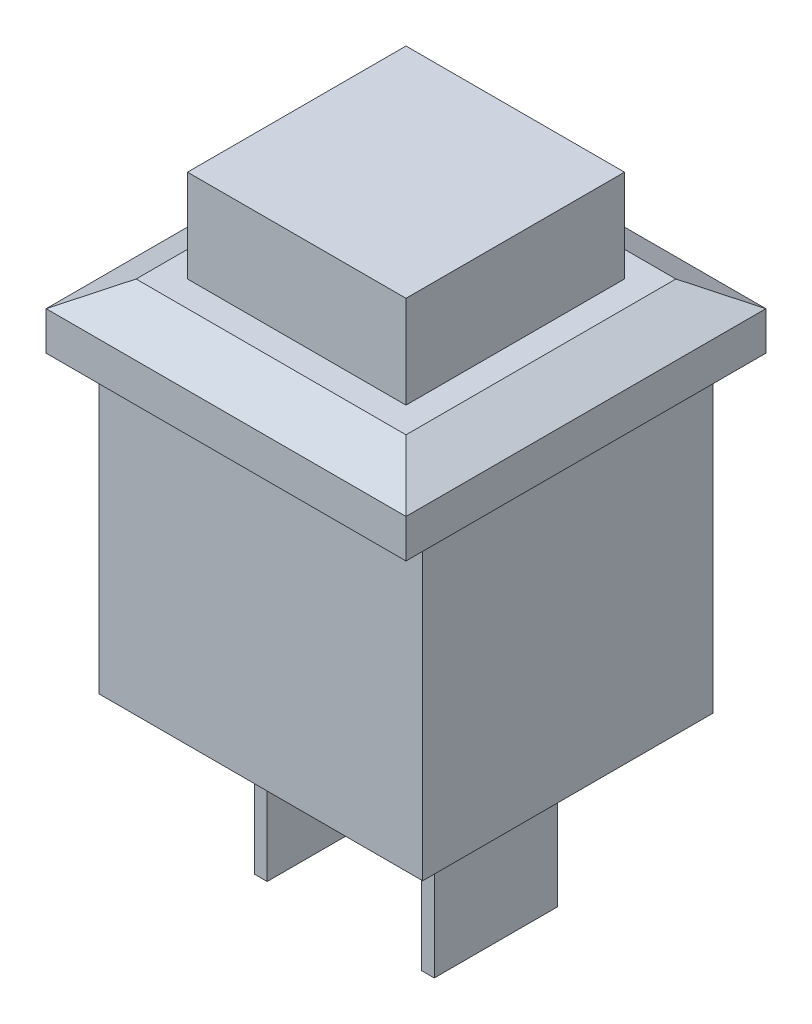
SolidWorks part; units mm, degrees
ref_plane "Front Plane" through (0, 0, 0) normal (0, 0, 1) x (1, 0, 0)
ref_plane "Top Plane" through (0, 0, 0) normal (0, 1, 0) x (1, 0, 0)
ref_plane "Right Plane" through (0, 0, 0) normal (1, 0, 0) x (0, 0, -1)
sketch "Bezel drawing" plane through (0, 0, 0) normal (0, 1, 0) x (1, 0, 0)
  line L1 (-7, -7) -> (7, -7)
  line L2 (-7, -7) -> (-7, 7)
  line L3 (-7, 7) -> (7, 7)
  line L4 (7, -7) -> (7, 7)
  line L5 (-7, -7) -> (7, 7) construction
  line L6 (-7, 7) -> (7, -7) construction
  point P0 (0, 0)
  dimension "D1" = 14
  dimension "D2" = 14
extrude "Bezel" add sketch "Bezel drawing" along normal blind 2.5
chamfer "Chamfer1" distance 1 distance2 1.75 4 edges at (0, 2.5, 7) (-7, 2.5, 0) (0, 2.5, -7) (7, 2.5, 0) first distance on face at (0, 1.25, 7) first distance on face at (-7, 1.25, 0) first distance on face at (0, 1.25, -7) first distance on face at (7, 1.25, 0)
sketch "Sketch2" plane through (0, 2.5, 0) normal (0, 1, 0) x (1, 0, 0)
  line L1 (-4.25, 4.25) -> (4.25, 4.25)
  line L2 (-4.25, 4.25) -> (-4.25, -4.25)
  line L3 (-4.25, -4.25) -> (4.25, -4.25)
  line L4 (4.25, 4.25) -> (4.25, -4.25)
  line L5 (-4.25, 4.25) -> (4.25, -4.25) construction
  line L6 (-4.25, -4.25) -> (4.25, 4.25) construction
  point P0 (0, 0)
  dimension "D1" = 8.5
  dimension "D2" = 8.5
extrude "Boss-Extrude2" add sketch "Sketch2" along normal blind 3.6 separate body
sketch "Sketch3" plane through (0, 0, 0) normal (0, -1, 0) x (1, 0, 0)
  line L1 (6.3, -5.65) -> (-6.3, -5.65)
  line L2 (6.3, -5.65) -> (6.3, 5.65)
  line L3 (6.3, 5.65) -> (-6.3, 5.65)
  line L4 (-6.3, -5.65) -> (-6.3, 5.65)
  line L5 (6.3, -5.65) -> (-6.3, 5.65) construction
  line L6 (6.3, 5.65) -> (-6.3, -5.65) construction
  point P0 (0, 0)
  dimension "D1" = 12.6
  dimension "D2" = 11.3
extrude "Boss-Extrude3" add sketch "Sketch3" along normal blind 11.8
sketch "Sketch4" plane through (0, -11.8, 0) normal (0, -1, 0) x (1, 0, 0)
  line L0 (0, 0) -> (-8.7597, 0) construction
  line L1 (-3.5, -2.4) -> (-3, -2.4)
  line L2 (-3.5, -2.4) -> (-3.5, 2.4)
  line L3 (-3.5, 2.4) -> (-3, 2.4)
  line L4 (-3, -2.4) -> (-3, 2.4)
  line L5 (-3.5, -2.4) -> (-3, 2.4) construction
  line L6 (-3.5, 2.4) -> (-3, -2.4) construction
  line L7 (0, 0) -> (0, 4.4901) construction
  line L8 (3, -2.4) -> (3, 2.4)
  line L9 (3.5, -2.4) -> (3, -2.4)
  line L10 (3.5, -2.4) -> (3.5, 2.4)
  line L11 (3.5, 2.4) -> (3, 2.4)
  point P0 (-3.25, 0)
  dimension "D1" = 0.5
  dimension "D2" = 4.8
  dimension "D3" = 3.25
extrude "Boss-Extrude4" add sketch "Sketch4" along normal blind 6.3
ref_axis "Vertical Centerline" through (0, 0, 0) along (0, 0, -1)
ref_axis "Horizontal Centerline" through (0, 0, 0) along (-1, 0, 0)
